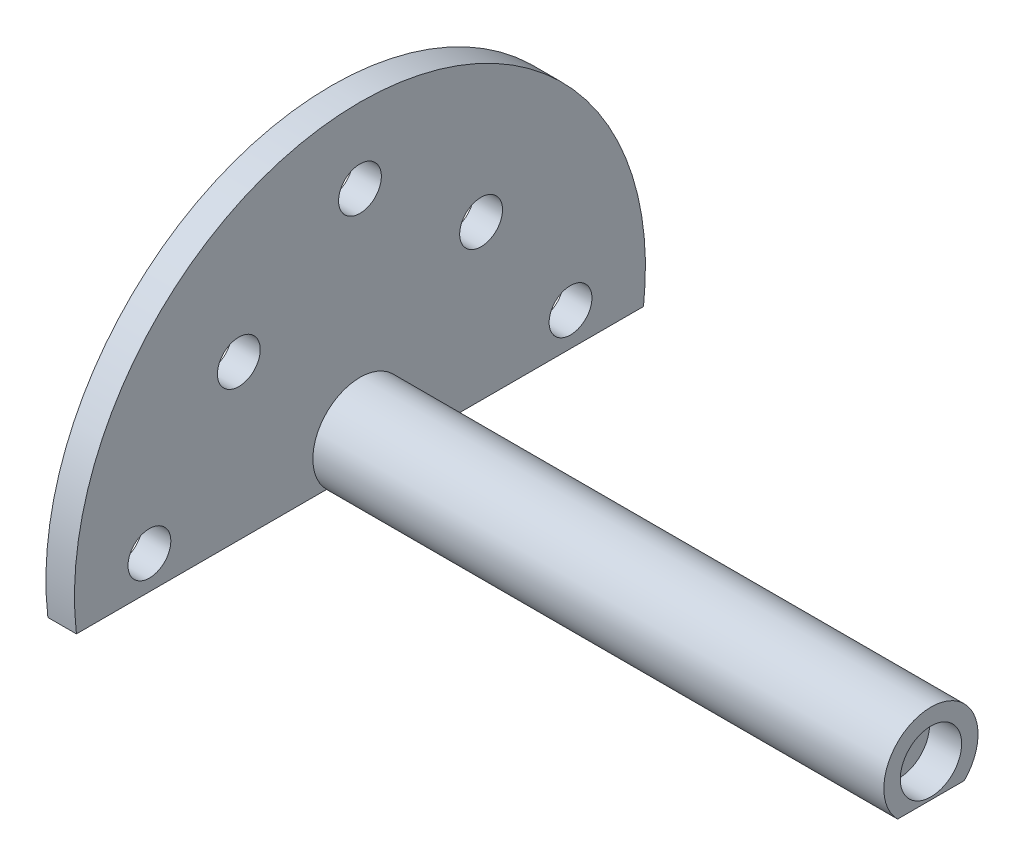
SolidWorks part; units mm, degrees
ref_plane "Front Plane" through (0, 0, 0) normal (0, 0, 1) x (1, 0, 0)
ref_plane "Top Plane" through (0, 0, 0) normal (0, 1, 0) x (1, 0, 0)
ref_plane "Right Plane" through (0, 0, 0) normal (1, 0, 0) x (0, 0, -1)
sketch "Sketch1" plane through (0, 0, 0) normal (1, 0, 0) x (0, 0, -1)
  line L0 (-8.4853, 8.4853) -> (-14.75, 0) construction
  line L1 (-8.4853, 8.4853) -> (0, 14.75) construction
  line L2 (-16.75, -2.3335) -> (-19.8634, -2.3335)
  line L3 (-16.75, -2.3335) -> (16.75, -2.3335)
  line L4 (-16.75, -2.3335) -> (-16.75, 16.75)
  line L5 (-16.75, 16.75) -> (16.75, 16.75)
  line L6 (16.75, -2.3335) -> (16.75, 16.75)
  line L7 (-2.3335, -2.3335) -> (2.3335, -2.3335)
  line L8 (-2.3335, -2.3335) -> (-2.3335, 2.3335)
  line L9 (-2.3335, 2.3335) -> (2.3335, 2.3335)
  line L10 (2.3335, -2.3335) -> (2.3335, 2.3335)
  line L11 (16.75, -2.3335) -> (19.8634, -2.3335)
  circle A0 centre (0, 0) radius 14.75 construction
  circle A1 centre (0, 14.75) radius 1.5
  circle A2 centre (0, 0) radius 14.75 construction
  circle A3 centre (14.75, 0) radius 1.5
  circle A4 centre (0, 0) radius 14.75 construction
  circle A5 centre (0, -14.75) radius 1.5 construction
  circle A6 centre (0, 0) radius 14.75 construction
  circle A7 centre (-14.75, 0) radius 1.5
  circle A8 centre (0, 0) radius 12 construction
  circle A9 centre (-8.4853, 8.4853) radius 1.5
  circle A10 centre (8.4853, 8.4853) radius 1.5
  circle A11 centre (8.4853, -8.4853) radius 1.5 construction
  circle A12 centre (-8.4853, -8.4853) radius 1.5 construction
  circle A13 centre (0, 0) radius 3.3
  circle A14 centre (0, 0) radius 20
  point P16 (0, 0)
  point P27 (0, 0)
  dimension "D1" = 4
  dimension "D2" = 4
  dimension "D3" = 2
  dimension "D6" = 3
  dimension "D7" = 6.6
  dimension "D8" = 29.5
  dimension "D9" = 24
  dimension "D10" = 40
  dimension "D4" = 2
  dimension "D5" = 2
extrude "Boss-Extrude1" add sketch "Sketch1" along normal blind 2 contours L3 L10 L9 L8 | L8 A13 | L9 A13 | L10 A13 | A13 L3 L6 L5 L4 A10 A9 A7 A3 A1 | L4 A14 L2 | L11 A14 L6 | L5 A14 region at (0, 7.246, 0) region at (0, 2.8901, 18.1289) region at (0, 0, 0) region at (0, 0, 2.7254) region at (0, 2.8901, -18.1289) region at (0, 0, -2.7254) region at (0, 2.7254, 0) region at (0, 18.0595, 0)
extrude "Boss-Extrude2" add sketch "Sketch1<3>" along normal blind 40 from surface contours L3 L10 L9 L8 | L10 A13 | L9 A13 | L8 A13 region at (0, 0, 0) region at (0, 0, 2.7254) region at (0, 0, -2.7254) region at (0, 2.7254, 0) starting at face at (2, 8.8333, 0)
sketch "Sketch1<3>" plane through (0, 0, 0) normal (1, 0, 0) x (0, 0, -1) same geometry as "Sketch1"
sketch "Sketch3" plane through (42, 0, 0) normal (1, 0, 0) x (0, 0, -1)
  circle A1 centre (0, 0) radius 2.15
extrude "Cut-Extrude1" cut sketch "Sketch3" against normal blind 2.25 contours A1
